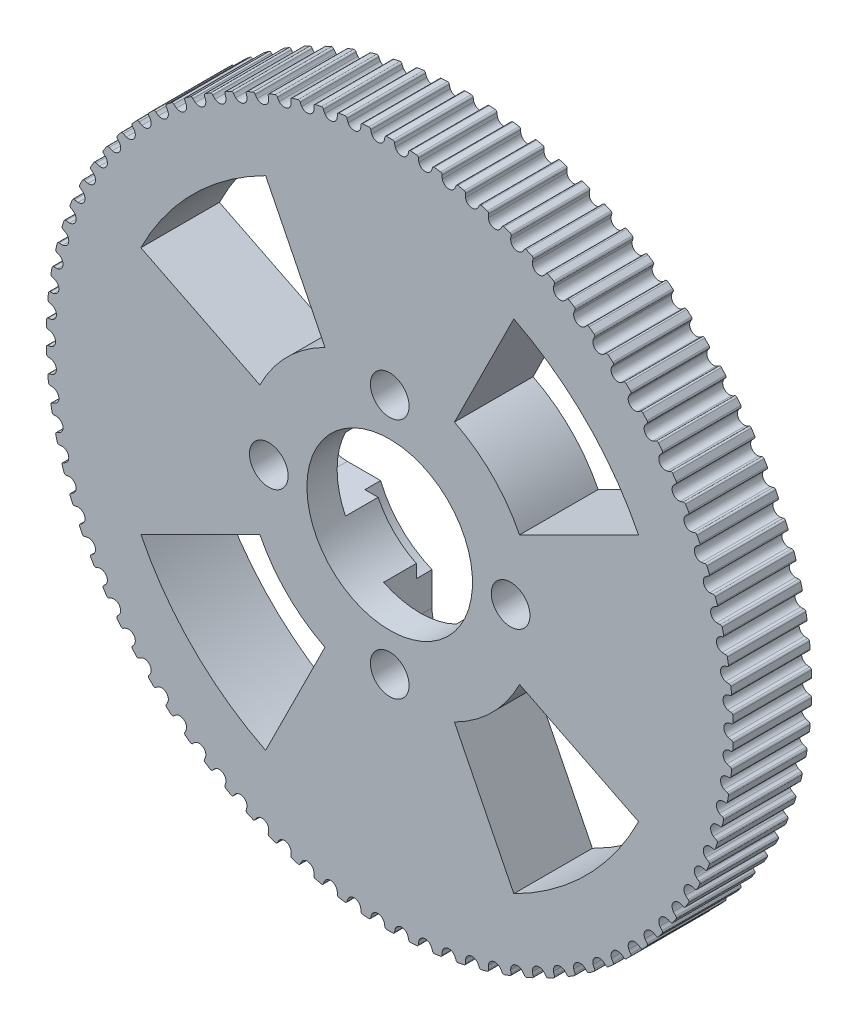
SolidWorks part; units mm, degrees
ref_plane "前视基准面" through (0, 0, 0) normal (0, 0, 1) x (1, 0, 0)
ref_plane "上视基准面" through (0, 0, 0) normal (0, 1, 0) x (1, 0, 0)
ref_plane "右视基准面" through (0, 0, 0) normal (1, 0, 0) x (0, 0, -1)
sketch "草图1" plane through (0, 0, 0) normal (0, 0, 1) x (1, 0, 0)
  line L0 (-10.0057, 26.1448) -> (-10.0057, 26.1386)
  line L1 (-10.0057, -26.1386) -> (-10.0057, -26.1448)
  arc A0 (27.4975, -7.1209) -> (27.6219, -6.6219) centre (0.0103, -0.0026) ccw
  arc A1 (27.6219, -6.6219) -> (27.626, -6.587) centre (27.476, -6.587) ccw
  arc A2 (27.626, -6.587) -> (27.5209, -6.4438) centre (27.476, -6.587) ccw
  arc A3 (27.2702, -6.3249) -> (27.5209, -6.4438) centre (27.82, -5.4896) ccw
  arc A4 (27.4851, -5.3137) -> (27.2702, -6.3249) centre (27.5753, -5.8613) ccw
  arc A5 (27.7625, -5.307) -> (27.4851, -5.3137) centre (27.6477, -6.3004) ccw
  arc A6 (27.7625, -5.307) -> (27.9272, -5.1854) centre (27.7797, -5.158) ccw
  arc A7 (27.9272, -5.1854) -> (28.0165, -4.679) centre (0.0105, -0.0018) ccw
  arc A8 (28.0165, -4.679) -> (28.0186, -4.6543) centre (27.8686, -4.6543) ccw
  arc A9 (28.0186, -4.6543) -> (27.9033, -4.5084) centre (27.8686, -4.6543) ccw
  arc A10 (27.6449, -4.4072) -> (27.9033, -4.5084) centre (28.1352, -3.5356) ccw
  arc A11 (27.7888, -3.3835) -> (27.6449, -4.4072) centre (27.917, -3.9235) ccw
  arc A12 (28.0651, -3.3575) -> (27.7888, -3.3835) centre (28.0198, -4.3564) ccw
  arc A13 (28.0651, -3.3575) -> (28.2209, -3.2247) centre (28.0719, -3.2076) ccw
  arc A14 (28.2209, -3.2247) -> (28.2747, -2.7133) centre (0.0106, -0.0011) ccw
  arc A15 (28.2747, -2.7133) -> (28.2753, -2.6989) centre (28.1253, -2.6989) ccw
  arc A16 (28.2753, -2.6989) -> (28.1499, -2.551) centre (28.1253, -2.6989) ccw
  arc A17 (27.885, -2.4681) -> (28.1499, -2.551) centre (28.3133, -1.5644) ccw
  arc A18 (27.9571, -1.4368) -> (27.885, -2.4681) centre (28.1227, -1.9665) ccw
  arc A19 (28.2309, -1.3916) -> (27.9571, -1.4368) centre (28.2554, -2.3913) ccw
  arc A20 (28.2309, -1.3916) -> (28.3771, -1.2482) centre (28.2272, -1.2416) ccw
  arc A21 (28.3771, -1.2482) -> (28.395, -0.7343) centre (0.0106, -0.0004) ccw
  arc A22 (28.395, -0.7343) -> (28.3951, -0.7304) centre (28.2451, -0.7304) ccw
  arc A23 (28.3951, -0.7304) -> (28.2592, -0.5811) centre (28.2451, -0.7304) ccw
  arc A24 (27.9893, -0.5169) -> (28.2592, -0.5811) centre (28.3534, 0.4144) ccw
  arc A25 (27.9893, 0.5169) -> (27.9893, -0.5169) centre (28.1914, 0) ccw
  arc A26 (28.2592, 0.5811) -> (27.9893, 0.5169) centre (28.3534, -0.4144) ccw
  arc A27 (28.2592, 0.5811) -> (28.3951, 0.7304) centre (28.2451, 0.7304) ccw
  arc A28 (28.3951, 0.7304) -> (28.395, 0.7343) centre (28.2451, 0.7304) ccw
  arc A29 (28.395, 0.7343) -> (28.3771, 1.2482) centre (0.0106, 0.0004) ccw
  arc A30 (28.3771, 1.2482) -> (28.2309, 1.3916) centre (28.2272, 1.2416) ccw
  arc A31 (27.9571, 1.4368) -> (28.2309, 1.3916) centre (28.2554, 2.3913) ccw
  arc A32 (27.885, 2.4681) -> (27.9571, 1.4368) centre (28.1227, 1.9665) ccw
  arc A33 (28.1499, 2.551) -> (27.885, 2.4681) centre (28.3133, 1.5644) ccw
  arc A34 (28.1499, 2.551) -> (28.2753, 2.6989) centre (28.1253, 2.6989) ccw
  arc A35 (28.2753, 2.6989) -> (28.2747, 2.7133) centre (28.1253, 2.6989) ccw
  arc A36 (28.2747, 2.7133) -> (28.2209, 3.2247) centre (0.0106, 0.0011) ccw
  arc A37 (28.2209, 3.2247) -> (28.0651, 3.3575) centre (28.0719, 3.2076) ccw
  arc A38 (27.7888, 3.3835) -> (28.0651, 3.3575) centre (28.0198, 4.3564) ccw
  arc A39 (27.6449, 4.4072) -> (27.7888, 3.3835) centre (27.917, 3.9235) ccw
  arc A40 (27.9033, 4.5084) -> (27.6449, 4.4072) centre (28.1352, 3.5356) ccw
  arc A41 (27.9033, 4.5084) -> (28.0186, 4.6543) centre (27.8686, 4.6543) ccw
  arc A42 (28.0186, 4.6543) -> (28.0165, 4.679) centre (27.8686, 4.6543) ccw
  arc A43 (28.0165, 4.679) -> (27.9272, 5.1854) centre (0.0105, 0.0018) ccw
  arc A44 (27.9272, 5.1854) -> (27.7625, 5.307) centre (27.7797, 5.158) ccw
  arc A45 (27.4851, 5.3137) -> (27.7625, 5.307) centre (27.6477, 6.3004) ccw
  arc A46 (27.2702, 6.3249) -> (27.4851, 5.3137) centre (27.5753, 5.8613) ccw
  arc A47 (27.5209, 6.4438) -> (27.2702, 6.3249) centre (27.82, 5.4896) ccw
  arc A48 (27.5209, 6.4438) -> (27.626, 6.587) centre (27.476, 6.587) ccw
  arc A49 (27.626, 6.587) -> (27.6219, 6.6219) centre (27.476, 6.587) ccw
  arc A50 (27.6219, 6.6219) -> (27.4975, 7.1209) centre (0.0103, 0.0026) ccw
  arc A51 (27.4975, 7.1209) -> (27.3247, 7.2307) centre (27.3523, 7.0833) ccw
  arc A52 (27.0475, 7.218) -> (27.3247, 7.2307) centre (27.1408, 8.2137) ccw
  arc A53 (26.7625, 8.2117) -> (27.0475, 7.218) centre (27.0993, 7.7706) ccw
  arc A54 (27.0043, 8.3479) -> (26.7625, 8.2117) centre (27.3693, 7.4169) ccw
  arc A55 (27.0043, 8.3479) -> (27.0996, 8.4876) centre (26.9496, 8.4876) ccw
  arc A56 (27.0996, 8.4876) -> (27.0927, 8.5326) centre (26.9496, 8.4876) ccw
  arc A57 (27.0927, 8.5326) -> (26.9338, 9.0216) centre (0.0101, 0.0033) ccw
  arc A58 (26.9338, 9.0216) -> (26.7537, 9.1192) centre (26.7915, 8.974) ccw
  arc A59 (26.4781, 9.0872) -> (26.7537, 9.1192) centre (26.5018, 10.0869) ccw
  arc A60 (26.1245, 10.0586) -> (26.4781, 9.0872) centre (26.4912, 9.642) ccw
  arc A61 (26.3562, 10.2113) -> (26.1245, 10.0586) centre (26.7853, 9.308) ccw
  arc A62 (26.3562, 10.2113) -> (26.4419, 10.3468) centre (26.2919, 10.3468) ccw
  arc A63 (26.4419, 10.3468) -> (26.4315, 10.4017) centre (26.2919, 10.3468) ccw
  arc A64 (26.4315, 10.4017) -> (26.2388, 10.8785) centre (0.0099, 0.004) ccw
  arc A65 (26.2388, 10.8785) -> (26.0524, 10.9632) centre (26.1003, 10.821) ccw
  arc A66 (25.7797, 10.9121) -> (26.0524, 10.9632) centre (25.7336, 11.911) ccw
  arc A67 (25.3592, 11.8565) -> (25.7797, 10.9121) centre (25.7541, 11.4665) ccw
  arc A68 (25.5797, 12.0249) -> (25.3592, 11.8565) centre (26.0707, 11.1538) ccw
  arc A69 (25.5797, 12.0249) -> (25.6561, 12.1556) centre (25.5061, 12.1556) ccw
  arc A70 (25.6561, 12.1556) -> (25.6415, 12.2201) centre (25.5061, 12.1556) ccw
  arc A71 (25.6415, 12.2201) -> (25.4161, 12.6823) centre (0.0096, 0.0047) ccw
  arc A72 (25.4161, 12.6823) -> (25.2242, 12.7538) centre (25.2819, 12.6153) ccw
  arc A73 (24.9557, 12.6838) -> (25.2242, 12.7538) centre (24.84, 13.6771) ccw
  arc A74 (24.4704, 13.5965) -> (24.9557, 12.6838) centre (24.8915, 13.235) ccw
  arc A75 (24.6786, 13.78) -> (24.4704, 13.5965) centre (25.2292, 12.9452) ccw
  arc A76 (24.6786, 13.78) -> (24.746, 13.9052) centre (24.596, 13.9052) ccw
  arc A77 (24.746, 13.9052) -> (24.7266, 13.979) centre (24.596, 13.9052) ccw
  arc A78 (24.7266, 13.979) -> (24.4695, 14.4243) centre (0.0092, 0.0053) ccw
  arc A79 (24.4695, 14.4243) -> (24.2731, 14.4823) centre (24.3403, 14.3482) ccw
  arc A80 (24.0101, 14.3937) -> (24.2731, 14.4823) centre (23.8254, 15.3765) ccw
  arc A81 (23.4623, 15.2704) -> (24.0101, 14.3937) centre (23.9076, 14.9391) ccw
  arc A82 (23.6572, 15.4679) -> (23.4623, 15.2704) centre (24.2647, 14.6736) ccw
  arc A83 (23.6572, 15.4679) -> (23.7161, 15.5871) centre (23.5661, 15.5871) ccw
  arc A84 (23.7161, 15.5871) -> (23.6912, 15.6698) centre (23.5661, 15.5871) ccw
  arc A85 (23.6912, 15.6698) -> (23.4037, 16.0961) centre (0.0088, 0.006) ccw
  arc A86 (23.4037, 16.0961) -> (23.2038, 16.1402) centre (23.2801, 16.0111) ccw
  arc A87 (22.9476, 16.0335) -> (23.2038, 16.1402) centre (22.6948, 17.001) ccw
  arc A88 (22.34, 16.8698) -> (22.9476, 16.0335) centre (22.8073, 16.5705) ccw
  arc A89 (22.5206, 17.0805) -> (22.34, 16.8698) centre (23.182, 16.3304) ccw
  arc A90 (22.5206, 17.0805) -> (22.5714, 17.193) centre (22.4214, 17.193) ccw
  arc A91 (22.5714, 17.193) -> (22.5405, 17.2843) centre (22.4214, 17.193) ccw
  arc A92 (22.5405, 17.2843) -> (22.2239, 17.6895) centre (0.0084, 0.0066) ccw
  arc A93 (22.2239, 17.6895) -> (22.0214, 17.7195) centre (22.1065, 17.596) ccw
  arc A94 (21.7733, 17.5952) -> (22.0214, 17.7195) centre (21.4536, 18.5427) ccw
  arc A95 (21.1088, 18.3871) -> (21.7733, 17.5952) centre (21.5958, 18.1211) ccw
  arc A96 (21.2743, 18.6098) -> (21.1088, 18.3871) centre (21.9864, 17.9077) ccw
  arc A97 (21.2743, 18.6098) -> (21.3175, 18.7152) centre (21.1675, 18.7152) ccw
  arc A98 (21.3175, 18.7152) -> (21.2799, 18.8145) centre (21.1675, 18.7152) ccw
  arc A99 (21.2799, 18.8145) -> (20.9358, 19.1966) centre (0.0079, 0.0071) ccw
  arc A100 (20.9358, 19.1966) -> (20.7317, 19.2125) centre (20.8252, 19.0953) ccw
  arc A101 (20.4928, 19.0711) -> (20.7317, 19.2125) centre (20.1079, 19.9941) ccw
  arc A102 (19.7747, 19.8148) -> (20.4928, 19.0711) centre (20.2792, 19.5834) ccw
  arc A103 (19.9243, 20.0485) -> (19.7747, 19.8148) centre (20.6836, 19.3978) ccw
  arc A104 (19.9243, 20.0485) -> (19.9604, 20.1461) centre (19.8104, 20.1461) ccw
  arc A105 (19.9604, 20.1461) -> (19.9156, 20.2531) centre (19.8104, 20.1461) ccw
  arc A106 (19.9156, 20.2531) -> (19.5457, 20.6103) centre (0.0074, 0.0077) ccw
  arc A107 (19.5457, 20.6103) -> (19.341, 20.6119) centre (19.4425, 20.5014) ccw
  arc A108 (19.1126, 20.4542) -> (19.341, 20.6119) centre (18.6642, 21.348) ccw
  arc A109 (18.3443, 21.1459) -> (19.1126, 20.4542) centre (18.8637, 20.9503) ccw
  arc A110 (18.4773, 21.3895) -> (18.3443, 21.1459) centre (19.2801, 20.7934) ccw
  arc A111 (18.4773, 21.3895) -> (18.5068, 21.479) centre (18.3568, 21.479) ccw
  arc A112 (18.5068, 21.479) -> (18.4543, 21.593) centre (18.3568, 21.479) ccw
  arc A113 (18.4543, 21.593) -> (18.0604, 21.9235) centre (0.0068, 0.0082) ccw
  arc A114 (18.0604, 21.9235) -> (17.856, 21.9108) centre (17.965, 21.8077) ccw
  arc A115 (17.6392, 21.7376) -> (17.856, 21.9108) centre (17.1295, 22.598) ccw
  arc A116 (16.8246, 22.3741) -> (17.6392, 21.7376) centre (17.3563, 22.2151) ccw
  arc A117 (16.9402, 22.6263) -> (16.8246, 22.3741) centre (17.7827, 22.0876) ccw
  arc A118 (16.9402, 22.6263) -> (16.9638, 22.7071) centre (16.8138, 22.7071) ccw
  arc A119 (16.9638, 22.7071) -> (16.9031, 22.8277) centre (16.8138, 22.7071) ccw
  arc A120 (16.9031, 22.8277) -> (16.4871, 23.1299) centre (0.0063, 0.0086) ccw
  arc A121 (16.4871, 23.1299) -> (16.2841, 23.103) centre (16.4, 23.0078) ccw
  arc A122 (16.0799, 22.9151) -> (16.2841, 23.103) centre (15.5114, 23.7378) ccw
  arc A123 (15.2229, 23.4932) -> (16.0799, 22.9151) centre (15.7644, 23.3717) ccw
  arc A124 (15.3206, 23.7529) -> (15.2229, 23.4932) centre (16.1986, 23.2743) ccw
  arc A125 (15.3206, 23.7529) -> (15.3389, 23.8247) centre (15.1889, 23.8247) ccw
  arc A126 (15.3389, 23.8247) -> (15.2695, 23.9512) centre (15.1889, 23.8247) ccw
  arc A127 (15.2695, 23.9512) -> (14.8335, 24.2237) centre (0.0056, 0.009) ccw
  arc A128 (14.8335, 24.2237) -> (14.6329, 24.1827) centre (14.7551, 24.0957) ccw
  arc A129 (14.4423, 23.981) -> (14.6329, 24.1827) centre (13.8178, 24.762) ccw
  arc A130 (13.547, 24.4978) -> (14.4423, 23.981) centre (14.0957, 24.4144) ccw
  arc A131 (13.6264, 24.7638) -> (13.547, 24.4978) centre (14.5356, 24.3476) ccw
  arc A132 (13.6264, 24.7638) -> (13.64, 24.8262) centre (13.49, 24.8262) ccw
  arc A133 (13.64, 24.8262) -> (13.5616, 24.958) centre (13.49, 24.8262) ccw
  arc A134 (13.5616, 24.958) -> (13.1076, 25.1994) centre (0.005, 0.0094) ccw
  arc A135 (13.1076, 25.1994) -> (12.9103, 25.1445) centre (13.0384, 25.0663) ccw
  arc A136 (12.7343, 24.93) -> (12.9103, 25.1445) centre (12.0568, 25.6656) ccw
  arc A137 (11.8051, 25.3832) -> (12.7343, 24.93) centre (12.3583, 25.3382) ccw
  arc A138 (11.8657, 25.654) -> (11.8051, 25.3832) centre (12.8018, 25.3022) ccw
  arc A139 (11.8657, 25.654) -> (11.8753, 25.7067) centre (11.7253, 25.7067) ccw
  arc A140 (11.8753, 25.7067) -> (11.7876, 25.8432) centre (11.7253, 25.7067) ccw
  arc A141 (11.7876, 25.8432) -> (11.3178, 26.0523) centre (0.0043, 0.0097) ccw
  arc A142 (11.3178, 26.0523) -> (11.1249, 25.9838) centre (11.2581, 25.9148) ccw
  arc A143 (10.9642, 25.7576) -> (11.1249, 25.9838) centre (10.2371, 26.4441) ccw
  arc A144 (10.0057, 26.1448) -> (10.9642, 25.7576) centre (10.5607, 26.1386) ccw
  arc A145 (10.0473, 26.4192) -> (10.0057, 26.1448) centre (11.0056, 26.1336) ccw
  arc A146 (10.0473, 26.4192) -> (10.0535, 26.462) centre (9.9035, 26.462) ccw
  arc A147 (10.0535, 26.462) -> (9.9561, 26.6025) centre (9.9035, 26.462) ccw
  arc A148 (9.9561, 26.6025) -> (9.4729, 26.7784) centre (0.0036, 0.01) ccw
  arc A149 (9.4729, 26.7784) -> (9.2853, 26.6965) centre (9.4229, 26.637) ccw
  arc A150 (9.1407, 26.4596) -> (9.2853, 26.6965) centre (8.3675, 27.0938) ccw
  arc A151 (8.1576, 26.7791) -> (9.1407, 26.4596) centre (8.7116, 26.8116) ccw
  arc A152 (8.1558, 26.8376) -> (8.1576, 26.7791) centre (9.1558, 26.8376) ccw
  arc A153 (8.1799, 27.0557) -> (8.1558, 26.8376) centre (9.1558, 26.8376) ccw
  arc A154 (8.1799, 27.0557) -> (8.1835, 27.0884) centre (8.0335, 27.0884) ccw
  arc A155 (8.1835, 27.0884) -> (8.0762, 27.2322) centre (8.0335, 27.0884) ccw
  arc A156 (8.0762, 27.2322) -> (7.5819, 27.3739) centre (0.0029, 0.0102) ccw
  arc A157 (7.5819, 27.3739) -> (7.4004, 27.2792) centre (7.5419, 27.2294) ccw
  arc A158 (7.2727, 27.0328) -> (7.4004, 27.2792) centre (6.4572, 27.6115) ccw
  arc A159 (6.2697, 27.2829) -> (7.2727, 27.0328) centre (6.8201, 27.354) ccw
  arc A160 (6.2614, 27.4109) -> (6.2697, 27.2829) centre (7.2614, 27.4109) ccw
  arc A161 (6.2727, 27.5604) -> (6.2614, 27.4109) centre (7.2614, 27.4109) ccw
  arc A162 (6.2727, 27.5604) -> (6.2744, 27.5828) centre (6.1244, 27.5828) ccw
  arc A163 (6.2744, 27.5828) -> (6.1569, 27.7292) centre (6.1244, 27.5828) ccw
  arc A164 (6.1569, 27.7292) -> (5.6539, 27.8361) centre (0.0022, 0.0104) ccw
  arc A165 (5.6539, 27.8361) -> (5.4794, 27.729) centre (5.6241, 27.6892) ccw
  arc A166 (5.3693, 27.4743) -> (5.4794, 27.729) centre (4.5154, 27.9946) ccw
  arc A167 (4.3512, 27.6538) -> (5.3693, 27.4743) centre (4.8954, 27.7631) ccw
  arc A168 (4.3317, 27.8507) -> (4.3512, 27.6538) centre (5.3317, 27.8507) ccw
  arc A169 (4.3349, 27.9308) -> (4.3317, 27.8507) centre (5.3317, 27.8507) ccw
  arc A170 (4.3349, 27.9308) -> (4.3354, 27.9428) centre (4.1854, 27.9428) ccw
  arc A171 (4.3354, 27.9428) -> (4.2076, 28.0912) centre (4.1854, 27.9428) ccw
  arc A172 (4.2076, 28.0912) -> (3.6984, 28.1627) centre (0.0015, 0.0105) ccw
  arc A173 (3.6984, 28.1627) -> (3.5318, 28.0437) centre (3.6789, 28.014) ccw
  arc A174 (3.4397, 27.7819) -> (3.5318, 28.0437) centre (2.5516, 28.2414) ccw
  arc A175 (2.4116, 27.89) -> (3.4397, 27.7819) centre (2.9468, 28.0369) ccw
  arc A176 (2.3759, 28.1548) -> (2.4116, 27.89) centre (3.3759, 28.1548) ccw
  arc A177 (2.376, 28.1652) -> (2.3759, 28.1548) centre (3.3759, 28.1548) ccw
  arc A178 (2.376, 28.1652) -> (2.2378, 28.3163) centre (2.226, 28.1667) ccw
  arc A179 (2.2378, 28.3163) -> (1.7248, 28.3521) centre (0.0007, 0.0106) ccw
  arc A180 (1.7248, 28.3521) -> (1.567, 28.2217) centre (1.7157, 28.2024) ccw
  arc A181 (1.4934, 27.9542) -> (1.567, 28.2217) centre (0.5753, 28.3506) ccw
  arc A182 (0.4602, 27.9902) -> (1.4934, 27.9542) centre (0.9839, 28.1742) ccw
  arc A183 (0.4055, 28.2623) -> (0.4602, 27.9902) centre (1.4037, 28.3217) ccw
  arc A184 (0.4055, 28.2623) -> (0.2571, 28.4034) centre (0.2557, 28.2534) ccw
  arc A185 (0.2571, 28.4034) -> (-0.2571, 28.4034) centre (0, 0.0107) ccw
  arc A186 (-0.2571, 28.4034) -> (-0.4055, 28.2623) centre (-0.2557, 28.2534) ccw
  arc A187 (-0.4602, 27.9902) -> (-0.4055, 28.2623) centre (-1.4037, 28.3217) ccw
  arc A188 (-1.4934, 27.9542) -> (-0.4602, 27.9902) centre (-0.9839, 28.1742) ccw
  arc A189 (-1.567, 28.2217) -> (-1.4934, 27.9542) centre (-0.5753, 28.3506) ccw
  arc A190 (-1.567, 28.2217) -> (-1.7248, 28.3521) centre (-1.7157, 28.2024) ccw
  arc A191 (-1.7248, 28.3521) -> (-2.2378, 28.3163) centre (-0.0007, 0.0106) ccw
  arc A192 (-2.2378, 28.3163) -> (-2.376, 28.1652) centre (-2.226, 28.1667) ccw
  arc A193 (-2.4116, 27.89) -> (-2.376, 28.1652) centre (-3.3759, 28.1548) ccw
  arc A194 (-3.4397, 27.7819) -> (-2.4116, 27.89) centre (-2.9468, 28.0369) ccw
  arc A195 (-3.5318, 28.0437) -> (-3.4397, 27.7819) centre (-2.5516, 28.2414) ccw
  arc A196 (-3.5318, 28.0437) -> (-3.6984, 28.1627) centre (-3.6789, 28.014) ccw
  arc A197 (-3.6984, 28.1627) -> (-4.2076, 28.0912) centre (-0.0015, 0.0105) ccw
  arc A198 (-4.2076, 28.0912) -> (-4.3349, 27.9308) centre (-4.1854, 27.9428) ccw
  arc A199 (-4.3512, 27.6538) -> (-4.3349, 27.9308) centre (-5.3317, 27.8507) ccw
  arc A200 (-5.3693, 27.4743) -> (-4.3512, 27.6538) centre (-4.8954, 27.7631) ccw
  arc A201 (-5.4794, 27.729) -> (-5.3693, 27.4743) centre (-4.5154, 27.9946) ccw
  arc A202 (-5.4794, 27.729) -> (-5.6539, 27.8361) centre (-5.6241, 27.6892) ccw
  arc A203 (-5.6539, 27.8361) -> (-6.1569, 27.7292) centre (-0.0022, 0.0104) ccw
  arc A204 (-6.1569, 27.7292) -> (-6.2727, 27.5604) centre (-6.1244, 27.5828) ccw
  arc A205 (-6.2697, 27.2829) -> (-6.2727, 27.5604) centre (-7.2614, 27.4109) ccw
  arc A206 (-7.2727, 27.0328) -> (-6.2697, 27.2829) centre (-6.8201, 27.354) ccw
  arc A207 (-7.4004, 27.2792) -> (-7.2727, 27.0328) centre (-6.4572, 27.6115) ccw
  arc A208 (-7.4004, 27.2792) -> (-7.5819, 27.3739) centre (-7.5419, 27.2294) ccw
  arc A209 (-7.5819, 27.3739) -> (-8.0762, 27.2322) centre (-0.0029, 0.0102) ccw
  arc A210 (-8.0762, 27.2322) -> (-8.1799, 27.0557) centre (-8.0335, 27.0884) ccw
  arc A211 (-8.1576, 26.7791) -> (-8.1799, 27.0557) centre (-9.1558, 26.8376) ccw
  arc A212 (-9.1407, 26.4596) -> (-8.1576, 26.7791) centre (-8.7116, 26.8116) ccw
  arc A213 (-9.2853, 26.6965) -> (-9.1407, 26.4596) centre (-8.3675, 27.0938) ccw
  arc A214 (-9.2853, 26.6965) -> (-9.4729, 26.7784) centre (-9.4229, 26.637) ccw
  arc A215 (-9.4729, 26.7784) -> (-9.9561, 26.6025) centre (-0.0036, 0.01) ccw
  arc A216 (-9.9561, 26.6025) -> (-10.0473, 26.4192) centre (-9.9035, 26.462) ccw
  arc A217 (-10.0057, 26.1448) -> (-10.0473, 26.4192) centre (-11.0056, 26.1336) ccw
  arc A218 (-10.9642, 25.7576) -> (-10.0057, 26.1386) centre (-10.5607, 26.1386) ccw
  arc A219 (-11.1249, 25.9838) -> (-10.9642, 25.7576) centre (-10.2371, 26.4441) ccw
  arc A220 (-11.1249, 25.9838) -> (-11.3178, 26.0523) centre (-11.2581, 25.9148) ccw
  arc A221 (-11.3178, 26.0523) -> (-11.7876, 25.8432) centre (-0.0043, 0.0097) ccw
  arc A222 (-11.7876, 25.8432) -> (-11.8657, 25.654) centre (-11.7253, 25.7067) ccw
  arc A223 (-11.8051, 25.3832) -> (-11.8657, 25.654) centre (-12.8018, 25.3022) ccw
  arc A224 (-11.8033, 25.3382) -> (-11.8051, 25.3832) centre (-12.3583, 25.3382) ccw
  arc A225 (-12.7343, 24.93) -> (-11.8033, 25.3382) centre (-12.3583, 25.3382) ccw
  arc A226 (-12.9103, 25.1445) -> (-12.7343, 24.93) centre (-12.0568, 25.6656) ccw
  arc A227 (-12.9103, 25.1445) -> (-13.1076, 25.1994) centre (-13.0384, 25.0663) ccw
  arc A228 (-13.1076, 25.1994) -> (-13.5616, 24.958) centre (-0.005, 0.0094) ccw
  arc A229 (-13.5616, 24.958) -> (-13.6264, 24.7638) centre (-13.49, 24.8262) ccw
  arc A230 (-13.547, 24.4978) -> (-13.6264, 24.7638) centre (-14.5356, 24.3476) ccw
  arc A231 (-13.5407, 24.4144) -> (-13.547, 24.4978) centre (-14.0957, 24.4144) ccw
  arc A232 (-14.4423, 23.981) -> (-13.5407, 24.4144) centre (-14.0957, 24.4144) ccw
  arc A233 (-14.6329, 24.1827) -> (-14.4423, 23.981) centre (-13.8178, 24.762) ccw
  arc A234 (-14.6329, 24.1827) -> (-14.8335, 24.2237) centre (-14.7551, 24.0957) ccw
  arc A235 (-14.8335, 24.2237) -> (-15.2695, 23.9512) centre (-0.0056, 0.009) ccw
  arc A236 (-15.2695, 23.9512) -> (-15.3206, 23.7529) centre (-15.1889, 23.8247) ccw
  arc A237 (-15.2229, 23.4932) -> (-15.3206, 23.7529) centre (-16.1986, 23.2743) ccw
  arc A238 (-15.2094, 23.3717) -> (-15.2229, 23.4932) centre (-15.7644, 23.3717) ccw
  arc A239 (-16.0799, 22.9151) -> (-15.2094, 23.3717) centre (-15.7644, 23.3717) ccw
  arc A240 (-16.2841, 23.103) -> (-16.0799, 22.9151) centre (-15.5114, 23.7378) ccw
  arc A241 (-16.2841, 23.103) -> (-16.4871, 23.1299) centre (-16.4, 23.0078) ccw
  arc A242 (-16.4871, 23.1299) -> (-16.9031, 22.8277) centre (-0.0063, 0.0086) ccw
  arc A243 (-16.9031, 22.8277) -> (-16.9402, 22.6263) centre (-16.8138, 22.7071) ccw
  arc A244 (-16.8246, 22.3741) -> (-16.9402, 22.6263) centre (-17.7827, 22.0876) ccw
  arc A245 (-16.8013, 22.2151) -> (-16.8246, 22.3741) centre (-17.3563, 22.2151) ccw
  arc A246 (-17.6392, 21.7376) -> (-16.8013, 22.2151) centre (-17.3563, 22.2151) ccw
  arc A247 (-17.856, 21.9108) -> (-17.6392, 21.7376) centre (-17.1295, 22.598) ccw
  arc A248 (-17.856, 21.9108) -> (-18.0604, 21.9235) centre (-17.965, 21.8077) ccw
  arc A249 (-18.0604, 21.9235) -> (-18.4543, 21.593) centre (-0.0068, 0.0082) ccw
  arc A250 (-18.4543, 21.593) -> (-18.4773, 21.3895) centre (-18.3568, 21.479) ccw
  arc A251 (-18.3443, 21.1459) -> (-18.4773, 21.3895) centre (-19.2801, 20.7934) ccw
  arc A252 (-18.3087, 20.9503) -> (-18.3443, 21.1459) centre (-18.8637, 20.9503) ccw
  arc A253 (-19.1126, 20.4542) -> (-18.3087, 20.9503) centre (-18.8637, 20.9503) ccw
  arc A254 (-19.341, 20.6119) -> (-19.1126, 20.4542) centre (-18.6642, 21.348) ccw
  arc A255 (-19.341, 20.6119) -> (-19.5457, 20.6103) centre (-19.4425, 20.5014) ccw
  arc A256 (-19.5457, 20.6103) -> (-19.9156, 20.2531) centre (-0.0074, 0.0077) ccw
  arc A257 (-19.9156, 20.2531) -> (-19.9243, 20.0485) centre (-19.8104, 20.1461) ccw
  arc A258 (-19.7747, 19.8148) -> (-19.9243, 20.0485) centre (-20.6836, 19.3978) ccw
  arc A259 (-19.7242, 19.5834) -> (-19.7747, 19.8148) centre (-20.2792, 19.5834) ccw
  arc A260 (-20.4928, 19.0711) -> (-19.7242, 19.5834) centre (-20.2792, 19.5834) ccw
  arc A261 (-20.7317, 19.2125) -> (-20.4928, 19.0711) centre (-20.1079, 19.9941) ccw
  arc A262 (-20.7317, 19.2125) -> (-20.9358, 19.1966) centre (-20.8252, 19.0953) ccw
  arc A263 (-20.9358, 19.1966) -> (-21.2799, 18.8145) centre (-0.0079, 0.0071) ccw
  arc A264 (-21.2799, 18.8145) -> (-21.2743, 18.6098) centre (-21.1675, 18.7152) ccw
  arc A265 (-21.1088, 18.3871) -> (-21.2743, 18.6098) centre (-21.9864, 17.9077) ccw
  arc A266 (-21.0408, 18.1211) -> (-21.1088, 18.3871) centre (-21.5958, 18.1211) ccw
  arc A267 (-21.7733, 17.5952) -> (-21.0408, 18.1211) centre (-21.5958, 18.1211) ccw
  arc A268 (-22.0214, 17.7195) -> (-21.7733, 17.5952) centre (-21.4536, 18.5427) ccw
  arc A269 (-22.0214, 17.7195) -> (-22.2239, 17.6895) centre (-22.1065, 17.596) ccw
  arc A270 (-22.2239, 17.6895) -> (-22.5405, 17.2843) centre (-0.0084, 0.0066) ccw
  arc A271 (-22.5405, 17.2843) -> (-22.5206, 17.0805) centre (-22.4214, 17.193) ccw
  arc A272 (-22.34, 16.8698) -> (-22.5206, 17.0805) centre (-23.182, 16.3304) ccw
  arc A273 (-22.2523, 16.5705) -> (-22.34, 16.8698) centre (-22.8073, 16.5705) ccw
  arc A274 (-22.9476, 16.0335) -> (-22.2523, 16.5705) centre (-22.8073, 16.5705) ccw
  arc A275 (-23.2038, 16.1402) -> (-22.9476, 16.0335) centre (-22.6948, 17.001) ccw
  arc A276 (-23.2038, 16.1402) -> (-23.4037, 16.0961) centre (-23.2801, 16.0111) ccw
  arc A277 (-23.4037, 16.0961) -> (-23.6912, 15.6698) centre (-0.0088, 0.006) ccw
  arc A278 (-23.6912, 15.6698) -> (-23.6572, 15.4679) centre (-23.5661, 15.5871) ccw
  arc A279 (-23.4623, 15.2704) -> (-23.6572, 15.4679) centre (-24.2647, 14.6736) ccw
  arc A280 (-23.3526, 14.9391) -> (-23.4623, 15.2704) centre (-23.9076, 14.9391) ccw
  arc A281 (-24.0101, 14.3937) -> (-23.3526, 14.9391) centre (-23.9076, 14.9391) ccw
  arc A282 (-24.2731, 14.4823) -> (-24.0101, 14.3937) centre (-23.8254, 15.3765) ccw
  arc A283 (-24.2731, 14.4823) -> (-24.4695, 14.4243) centre (-24.3403, 14.3482) ccw
  arc A284 (-24.4695, 14.4243) -> (-24.7266, 13.979) centre (-0.0092, 0.0053) ccw
  arc A285 (-24.7266, 13.979) -> (-24.6786, 13.78) centre (-24.596, 13.9052) ccw
  arc A286 (-24.4704, 13.5965) -> (-24.6786, 13.78) centre (-25.2292, 12.9452) ccw
  arc A287 (-24.3365, 13.235) -> (-24.4704, 13.5965) centre (-24.8915, 13.235) ccw
  arc A288 (-24.9557, 12.6838) -> (-24.3365, 13.235) centre (-24.8915, 13.235) ccw
  arc A289 (-25.2242, 12.7538) -> (-24.9557, 12.6838) centre (-24.84, 13.6771) ccw
  arc A290 (-25.2242, 12.7538) -> (-25.4161, 12.6823) centre (-25.2819, 12.6153) ccw
  arc A291 (-25.4161, 12.6823) -> (-25.6415, 12.2201) centre (-0.0096, 0.0047) ccw
  arc A292 (-25.6415, 12.2201) -> (-25.5797, 12.0249) centre (-25.5061, 12.1556) ccw
  arc A293 (-25.3592, 11.8565) -> (-25.5797, 12.0249) centre (-26.0707, 11.1538) ccw
  arc A294 (-25.1991, 11.4665) -> (-25.3592, 11.8565) centre (-25.7541, 11.4665) ccw
  arc A295 (-25.7797, 10.9121) -> (-25.1991, 11.4665) centre (-25.7541, 11.4665) ccw
  arc A296 (-26.0524, 10.9632) -> (-25.7797, 10.9121) centre (-25.7336, 11.911) ccw
  arc A297 (-26.0524, 10.9632) -> (-26.2388, 10.8785) centre (-26.1003, 10.821) ccw
  arc A298 (-26.2388, 10.8785) -> (-26.4315, 10.4017) centre (-0.0099, 0.004) ccw
  arc A299 (-26.4315, 10.4017) -> (-26.3562, 10.2113) centre (-26.2919, 10.3468) ccw
  arc A300 (-26.1245, 10.0586) -> (-26.3562, 10.2113) centre (-26.7853, 9.308) ccw
  arc A301 (-25.9362, 9.642) -> (-26.1245, 10.0586) centre (-26.4912, 9.642) ccw
  arc A302 (-26.4781, 9.0872) -> (-25.9362, 9.642) centre (-26.4912, 9.642) ccw
  arc A303 (-26.7537, 9.1192) -> (-26.4781, 9.0872) centre (-26.5018, 10.0869) ccw
  arc A304 (-26.7537, 9.1192) -> (-26.9338, 9.0216) centre (-26.7915, 8.974) ccw
  arc A305 (-26.9338, 9.0216) -> (-27.0927, 8.5326) centre (-0.0101, 0.0033) ccw
  arc A306 (-27.0927, 8.5326) -> (-27.0043, 8.3479) centre (-26.9496, 8.4876) ccw
  arc A307 (-26.7625, 8.2117) -> (-27.0043, 8.3479) centre (-27.3693, 7.4169) ccw
  arc A308 (-26.5443, 7.7706) -> (-26.7625, 8.2117) centre (-27.0993, 7.7706) ccw
  arc A309 (-27.0475, 7.218) -> (-26.5443, 7.7706) centre (-27.0993, 7.7706) ccw
  arc A310 (-27.3247, 7.2307) -> (-27.0475, 7.218) centre (-27.1408, 8.2137) ccw
  arc A311 (-27.3247, 7.2307) -> (-27.4975, 7.1209) centre (-27.3523, 7.0833) ccw
  arc A312 (-27.4975, 7.1209) -> (-27.6219, 6.6219) centre (-0.0103, 0.0026) ccw
  arc A313 (-27.6219, 6.6219) -> (-27.5209, 6.4438) centre (-27.476, 6.587) ccw
  arc A314 (-27.2702, 6.3249) -> (-27.5209, 6.4438) centre (-27.82, 5.4896) ccw
  arc A315 (-27.0203, 5.8613) -> (-27.2702, 6.3249) centre (-27.5753, 5.8613) ccw
  arc A316 (-27.4851, 5.3137) -> (-27.0203, 5.8613) centre (-27.5753, 5.8613) ccw
  arc A317 (-27.7625, 5.307) -> (-27.4851, 5.3137) centre (-27.6477, 6.3004) ccw
  arc A318 (-27.7625, 5.307) -> (-27.9272, 5.1854) centre (-27.7797, 5.158) ccw
  arc A319 (-27.9272, 5.1854) -> (-28.0165, 4.679) centre (-0.0105, 0.0018) ccw
  arc A320 (-28.0165, 4.679) -> (-27.9033, 4.5084) centre (-27.8686, 4.6543) ccw
  arc A321 (-27.6449, 4.4072) -> (-27.9033, 4.5084) centre (-28.1352, 3.5356) ccw
  arc A322 (-27.362, 3.9235) -> (-27.6449, 4.4072) centre (-27.917, 3.9235) ccw
  arc A323 (-27.7888, 3.3835) -> (-27.362, 3.9235) centre (-27.917, 3.9235) ccw
  arc A324 (-28.0651, 3.3575) -> (-27.7888, 3.3835) centre (-28.0198, 4.3564) ccw
  arc A325 (-28.0651, 3.3575) -> (-28.2209, 3.2247) centre (-28.0719, 3.2076) ccw
  arc A326 (-28.2209, 3.2247) -> (-28.2747, 2.7133) centre (-0.0106, 0.0011) ccw
  arc A327 (-28.2747, 2.7133) -> (-28.1499, 2.551) centre (-28.1253, 2.6989) ccw
  arc A328 (-27.885, 2.4681) -> (-28.1499, 2.551) centre (-28.3133, 1.5644) ccw
  arc A329 (-27.5677, 1.9665) -> (-27.885, 2.4681) centre (-28.1227, 1.9665) ccw
  arc A330 (-27.9571, 1.4368) -> (-27.5677, 1.9665) centre (-28.1227, 1.9665) ccw
  arc A331 (-28.2309, 1.3916) -> (-27.9571, 1.4368) centre (-28.2554, 2.3913) ccw
  arc A332 (-28.2309, 1.3916) -> (-28.3771, 1.2482) centre (-28.2272, 1.2416) ccw
  arc A333 (-28.3771, 1.2482) -> (-28.395, 0.7343) centre (-0.0106, 0.0004) ccw
  arc A334 (-28.395, 0.7343) -> (-28.2592, 0.5811) centre (-28.2451, 0.7304) ccw
  arc A335 (-27.9893, 0.5169) -> (-28.2592, 0.5811) centre (-28.3534, -0.4144) ccw
  arc A336 (-27.6364, 0) -> (-27.9893, 0.5169) centre (-28.1914, 0) ccw
  arc A337 (-27.9893, -0.5169) -> (-27.6364, 0) centre (-28.1914, 0) ccw
  arc A338 (-28.2592, -0.5811) -> (-27.9893, -0.5169) centre (-28.3534, 0.4144) ccw
  arc A339 (-28.2592, -0.5811) -> (-28.395, -0.7343) centre (-28.2451, -0.7304) ccw
  arc A340 (-28.395, -0.7343) -> (-28.3771, -1.2482) centre (-0.0106, -0.0004) ccw
  arc A341 (-28.3771, -1.2482) -> (-28.2309, -1.3916) centre (-28.2272, -1.2416) ccw
  arc A342 (-27.9571, -1.4368) -> (-28.2309, -1.3916) centre (-28.2554, -2.3913) ccw
  arc A343 (-27.5677, -1.9665) -> (-27.9571, -1.4368) centre (-28.1227, -1.9665) ccw
  arc A344 (-27.885, -2.4681) -> (-27.5677, -1.9665) centre (-28.1227, -1.9665) ccw
  arc A345 (-28.1499, -2.551) -> (-27.885, -2.4681) centre (-28.3133, -1.5644) ccw
  arc A346 (-28.1499, -2.551) -> (-28.2747, -2.7133) centre (-28.1253, -2.6989) ccw
  arc A347 (-28.2747, -2.7133) -> (-28.2209, -3.2247) centre (-0.0106, -0.0011) ccw
  arc A348 (-28.2209, -3.2247) -> (-28.0651, -3.3575) centre (-28.0719, -3.2076) ccw
  arc A349 (-27.7888, -3.3835) -> (-28.0651, -3.3575) centre (-28.0198, -4.3564) ccw
  arc A350 (-27.362, -3.9235) -> (-27.7888, -3.3835) centre (-27.917, -3.9235) ccw
  arc A351 (-27.6449, -4.4072) -> (-27.362, -3.9235) centre (-27.917, -3.9235) ccw
  arc A352 (-27.9033, -4.5084) -> (-27.6449, -4.4072) centre (-28.1352, -3.5356) ccw
  arc A353 (-27.9033, -4.5084) -> (-28.0165, -4.679) centre (-27.8686, -4.6543) ccw
  arc A354 (-28.0165, -4.679) -> (-27.9272, -5.1854) centre (-0.0105, -0.0018) ccw
  arc A355 (-27.9272, -5.1854) -> (-27.7625, -5.307) centre (-27.7797, -5.158) ccw
  arc A356 (-27.4851, -5.3137) -> (-27.7625, -5.307) centre (-27.6477, -6.3004) ccw
  arc A357 (-27.0203, -5.8613) -> (-27.4851, -5.3137) centre (-27.5753, -5.8613) ccw
  arc A358 (-27.2702, -6.3249) -> (-27.0203, -5.8613) centre (-27.5753, -5.8613) ccw
  arc A359 (-27.5209, -6.4438) -> (-27.2702, -6.3249) centre (-27.82, -5.4896) ccw
  arc A360 (-27.5209, -6.4438) -> (-27.6219, -6.6219) centre (-27.476, -6.587) ccw
  arc A361 (-27.6219, -6.6219) -> (-27.4975, -7.1209) centre (-0.0103, -0.0026) ccw
  arc A362 (-27.4975, -7.1209) -> (-27.3247, -7.2307) centre (-27.3523, -7.0833) ccw
  arc A363 (-27.0475, -7.218) -> (-27.3247, -7.2307) centre (-27.1408, -8.2137) ccw
  arc A364 (-26.5443, -7.7706) -> (-27.0475, -7.218) centre (-27.0993, -7.7706) ccw
  arc A365 (-26.7625, -8.2117) -> (-26.5443, -7.7706) centre (-27.0993, -7.7706) ccw
  arc A366 (-27.0043, -8.3479) -> (-26.7625, -8.2117) centre (-27.3693, -7.4169) ccw
  arc A367 (-27.0043, -8.3479) -> (-27.0927, -8.5326) centre (-26.9496, -8.4876) ccw
  arc A368 (-27.0927, -8.5326) -> (-26.9338, -9.0216) centre (-0.0101, -0.0033) ccw
  arc A369 (-26.9338, -9.0216) -> (-26.7537, -9.1192) centre (-26.7915, -8.974) ccw
  arc A370 (-26.4781, -9.0872) -> (-26.7537, -9.1192) centre (-26.5018, -10.0869) ccw
  arc A371 (-25.9362, -9.642) -> (-26.4781, -9.0872) centre (-26.4912, -9.642) ccw
  arc A372 (-26.1245, -10.0586) -> (-25.9362, -9.642) centre (-26.4912, -9.642) ccw
  arc A373 (-26.3562, -10.2113) -> (-26.1245, -10.0586) centre (-26.7853, -9.308) ccw
  arc A374 (-26.3562, -10.2113) -> (-26.4315, -10.4017) centre (-26.2919, -10.3468) ccw
  arc A375 (-26.4315, -10.4017) -> (-26.2388, -10.8785) centre (-0.0099, -0.004) ccw
  arc A376 (-26.2388, -10.8785) -> (-26.0524, -10.9632) centre (-26.1003, -10.821) ccw
  arc A377 (-25.7797, -10.9121) -> (-26.0524, -10.9632) centre (-25.7336, -11.911) ccw
  arc A378 (-25.1991, -11.4665) -> (-25.7797, -10.9121) centre (-25.7541, -11.4665) ccw
  arc A379 (-25.3592, -11.8565) -> (-25.1991, -11.4665) centre (-25.7541, -11.4665) ccw
  arc A380 (-25.5797, -12.0249) -> (-25.3592, -11.8565) centre (-26.0707, -11.1538) ccw
  arc A381 (-25.5797, -12.0249) -> (-25.6415, -12.2201) centre (-25.5061, -12.1556) ccw
  arc A382 (-25.6415, -12.2201) -> (-25.4161, -12.6823) centre (-0.0096, -0.0047) ccw
  arc A383 (-25.4161, -12.6823) -> (-25.2242, -12.7538) centre (-25.2819, -12.6153) ccw
  arc A384 (-24.9557, -12.6838) -> (-25.2242, -12.7538) centre (-24.84, -13.6771) ccw
  arc A385 (-24.3365, -13.235) -> (-24.9557, -12.6838) centre (-24.8915, -13.235) ccw
  arc A386 (-24.4704, -13.5965) -> (-24.3365, -13.235) centre (-24.8915, -13.235) ccw
  arc A387 (-24.6786, -13.78) -> (-24.4704, -13.5965) centre (-25.2292, -12.9452) ccw
  arc A388 (-24.6786, -13.78) -> (-24.7266, -13.979) centre (-24.596, -13.9052) ccw
  arc A389 (-24.7266, -13.979) -> (-24.4695, -14.4243) centre (-0.0092, -0.0053) ccw
  arc A390 (-24.4695, -14.4243) -> (-24.2731, -14.4823) centre (-24.3403, -14.3482) ccw
  arc A391 (-24.0101, -14.3937) -> (-24.2731, -14.4823) centre (-23.8254, -15.3765) ccw
  arc A392 (-23.3526, -14.9391) -> (-24.0101, -14.3937) centre (-23.9076, -14.9391) ccw
  arc A393 (-23.4623, -15.2704) -> (-23.3526, -14.9391) centre (-23.9076, -14.9391) ccw
  arc A394 (-23.6572, -15.4679) -> (-23.4623, -15.2704) centre (-24.2647, -14.6736) ccw
  arc A395 (-23.6572, -15.4679) -> (-23.6912, -15.6698) centre (-23.5661, -15.5871) ccw
  arc A396 (-23.6912, -15.6698) -> (-23.4037, -16.0961) centre (-0.0088, -0.006) ccw
  arc A397 (-23.4037, -16.0961) -> (-23.2038, -16.1402) centre (-23.2801, -16.0111) ccw
  arc A398 (-22.9476, -16.0335) -> (-23.2038, -16.1402) centre (-22.6948, -17.001) ccw
  arc A399 (-22.2523, -16.5705) -> (-22.9476, -16.0335) centre (-22.8073, -16.5705) ccw
  arc A400 (-22.34, -16.8698) -> (-22.2523, -16.5705) centre (-22.8073, -16.5705) ccw
  arc A401 (-22.5206, -17.0805) -> (-22.34, -16.8698) centre (-23.182, -16.3304) ccw
  arc A402 (-22.5206, -17.0805) -> (-22.5405, -17.2843) centre (-22.4214, -17.193) ccw
  arc A403 (-22.5405, -17.2843) -> (-22.2239, -17.6895) centre (-0.0084, -0.0066) ccw
  arc A404 (-22.2239, -17.6895) -> (-22.0214, -17.7195) centre (-22.1065, -17.596) ccw
  arc A405 (-21.7733, -17.5952) -> (-22.0214, -17.7195) centre (-21.4536, -18.5427) ccw
  arc A406 (-21.0408, -18.1211) -> (-21.7733, -17.5952) centre (-21.5958, -18.1211) ccw
  arc A407 (-21.1088, -18.3871) -> (-21.0408, -18.1211) centre (-21.5958, -18.1211) ccw
  arc A408 (-21.2743, -18.6098) -> (-21.1088, -18.3871) centre (-21.9864, -17.9077) ccw
  arc A409 (-21.2743, -18.6098) -> (-21.2799, -18.8145) centre (-21.1675, -18.7152) ccw
  arc A410 (-21.2799, -18.8145) -> (-20.9358, -19.1966) centre (-0.0079, -0.0071) ccw
  arc A411 (-20.9358, -19.1966) -> (-20.7317, -19.2125) centre (-20.8252, -19.0953) ccw
  arc A412 (-20.4928, -19.0711) -> (-20.7317, -19.2125) centre (-20.1079, -19.9941) ccw
  arc A413 (-19.7242, -19.5834) -> (-20.4928, -19.0711) centre (-20.2792, -19.5834) ccw
  arc A414 (-19.7747, -19.8148) -> (-19.7242, -19.5834) centre (-20.2792, -19.5834) ccw
  arc A415 (-19.9243, -20.0485) -> (-19.7747, -19.8148) centre (-20.6836, -19.3978) ccw
  arc A416 (-19.9243, -20.0485) -> (-19.9156, -20.2531) centre (-19.8104, -20.1461) ccw
  arc A417 (-19.9156, -20.2531) -> (-19.5457, -20.6103) centre (-0.0074, -0.0077) ccw
  arc A418 (-19.5457, -20.6103) -> (-19.341, -20.6119) centre (-19.4425, -20.5014) ccw
  arc A419 (-19.1126, -20.4542) -> (-19.341, -20.6119) centre (-18.6642, -21.348) ccw
  arc A420 (-18.3087, -20.9503) -> (-19.1126, -20.4542) centre (-18.8637, -20.9503) ccw
  arc A421 (-18.3443, -21.1459) -> (-18.3087, -20.9503) centre (-18.8637, -20.9503) ccw
  arc A422 (-18.4773, -21.3895) -> (-18.3443, -21.1459) centre (-19.2801, -20.7934) ccw
  arc A423 (-18.4773, -21.3895) -> (-18.4543, -21.593) centre (-18.3568, -21.479) ccw
  arc A424 (-18.4543, -21.593) -> (-18.0604, -21.9235) centre (-0.0068, -0.0082) ccw
  arc A425 (-18.0604, -21.9235) -> (-17.856, -21.9108) centre (-17.965, -21.8077) ccw
  arc A426 (-17.6392, -21.7376) -> (-17.856, -21.9108) centre (-17.1295, -22.598) ccw
  arc A427 (-16.8013, -22.2151) -> (-17.6392, -21.7376) centre (-17.3563, -22.2151) ccw
  arc A428 (-16.8246, -22.3741) -> (-16.8013, -22.2151) centre (-17.3563, -22.2151) ccw
  arc A429 (-16.9402, -22.6263) -> (-16.8246, -22.3741) centre (-17.7827, -22.0876) ccw
  arc A430 (-16.9402, -22.6263) -> (-16.9031, -22.8277) centre (-16.8138, -22.7071) ccw
  arc A431 (-16.9031, -22.8277) -> (-16.4871, -23.1299) centre (-0.0063, -0.0086) ccw
  arc A432 (-16.4871, -23.1299) -> (-16.2841, -23.103) centre (-16.4, -23.0078) ccw
  arc A433 (-16.0799, -22.9151) -> (-16.2841, -23.103) centre (-15.5114, -23.7378) ccw
  arc A434 (-15.2094, -23.3717) -> (-16.0799, -22.9151) centre (-15.7644, -23.3717) ccw
  arc A435 (-15.2229, -23.4932) -> (-15.2094, -23.3717) centre (-15.7644, -23.3717) ccw
  arc A436 (-15.3206, -23.7529) -> (-15.2229, -23.4932) centre (-16.1986, -23.2743) ccw
  arc A437 (-15.3206, -23.7529) -> (-15.2695, -23.9512) centre (-15.1889, -23.8247) ccw
  arc A438 (-15.2695, -23.9512) -> (-14.8335, -24.2237) centre (-0.0056, -0.009) ccw
  arc A439 (-14.8335, -24.2237) -> (-14.6329, -24.1827) centre (-14.7551, -24.0957) ccw
  arc A440 (-14.4423, -23.981) -> (-14.6329, -24.1827) centre (-13.8178, -24.762) ccw
  arc A441 (-13.5407, -24.4144) -> (-14.4423, -23.981) centre (-14.0957, -24.4144) ccw
  arc A442 (-13.547, -24.4978) -> (-13.5407, -24.4144) centre (-14.0957, -24.4144) ccw
  arc A443 (-13.6264, -24.7638) -> (-13.547, -24.4978) centre (-14.5356, -24.3476) ccw
  arc A444 (-13.6264, -24.7638) -> (-13.5616, -24.958) centre (-13.49, -24.8262) ccw
  arc A445 (-13.5616, -24.958) -> (-13.1076, -25.1994) centre (-0.005, -0.0094) ccw
  arc A446 (-13.1076, -25.1994) -> (-12.9103, -25.1445) centre (-13.0384, -25.0663) ccw
  arc A447 (-12.7343, -24.93) -> (-12.9103, -25.1445) centre (-12.0568, -25.6656) ccw
  arc A448 (-11.8033, -25.3382) -> (-12.7343, -24.93) centre (-12.3583, -25.3382) ccw
  arc A449 (-11.8051, -25.3832) -> (-11.8033, -25.3382) centre (-12.3583, -25.3382) ccw
  arc A450 (-11.8657, -25.654) -> (-11.8051, -25.3832) centre (-12.8018, -25.3022) ccw
  arc A451 (-11.8657, -25.654) -> (-11.7876, -25.8432) centre (-11.7253, -25.7067) ccw
  arc A452 (-11.7876, -25.8432) -> (-11.3178, -26.0523) centre (-0.0043, -0.0097) ccw
  arc A453 (-11.3178, -26.0523) -> (-11.1249, -25.9838) centre (-11.2581, -25.9148) ccw
  arc A454 (-10.9642, -25.7576) -> (-11.1249, -25.9838) centre (-10.2371, -26.4441) ccw
  arc A455 (-10.0057, -26.1386) -> (-10.9642, -25.7576) centre (-10.5607, -26.1386) ccw
  arc A456 (-10.0473, -26.4192) -> (-10.0057, -26.1448) centre (-11.0056, -26.1336) ccw
  arc A457 (-10.0473, -26.4192) -> (-9.9561, -26.6025) centre (-9.9035, -26.462) ccw
  arc A458 (-9.9561, -26.6025) -> (-9.4729, -26.7784) centre (-0.0036, -0.01) ccw
  arc A459 (-9.4729, -26.7784) -> (-9.2853, -26.6965) centre (-9.4229, -26.637) ccw
  arc A460 (-9.1407, -26.4596) -> (-9.2853, -26.6965) centre (-8.3675, -27.0938) ccw
  arc A461 (-8.1576, -26.7791) -> (-9.1407, -26.4596) centre (-8.7116, -26.8116) ccw
  arc A462 (-8.1799, -27.0557) -> (-8.1576, -26.7791) centre (-9.1558, -26.8376) ccw
  arc A463 (-8.1799, -27.0557) -> (-8.0762, -27.2322) centre (-8.0335, -27.0884) ccw
  arc A464 (-8.0762, -27.2322) -> (-7.5819, -27.3739) centre (-0.0029, -0.0102) ccw
  arc A465 (-7.5819, -27.3739) -> (-7.4004, -27.2792) centre (-7.5419, -27.2294) ccw
  arc A466 (-7.2727, -27.0328) -> (-7.4004, -27.2792) centre (-6.4572, -27.6115) ccw
  arc A467 (-6.2697, -27.2829) -> (-7.2727, -27.0328) centre (-6.8201, -27.354) ccw
  arc A468 (-6.2727, -27.5604) -> (-6.2697, -27.2829) centre (-7.2614, -27.4109) ccw
  arc A469 (-6.2727, -27.5604) -> (-6.1569, -27.7292) centre (-6.1244, -27.5828) ccw
  arc A470 (-6.1569, -27.7292) -> (-5.6539, -27.8361) centre (-0.0022, -0.0104) ccw
  arc A471 (-5.6539, -27.8361) -> (-5.4794, -27.729) centre (-5.6241, -27.6892) ccw
  arc A472 (-5.3693, -27.4743) -> (-5.4794, -27.729) centre (-4.5154, -27.9946) ccw
  arc A473 (-4.3512, -27.6538) -> (-5.3693, -27.4743) centre (-4.8954, -27.7631) ccw
  arc A474 (-4.3349, -27.9308) -> (-4.3512, -27.6538) centre (-5.3317, -27.8507) ccw
  arc A475 (-4.3349, -27.9308) -> (-4.2076, -28.0912) centre (-4.1854, -27.9428) ccw
  arc A476 (-4.2076, -28.0912) -> (-3.6984, -28.1627) centre (-0.0015, -0.0105) ccw
  arc A477 (-3.6984, -28.1627) -> (-3.5318, -28.0437) centre (-3.6789, -28.014) ccw
  arc A478 (-3.4397, -27.7819) -> (-3.5318, -28.0437) centre (-2.5516, -28.2414) ccw
  arc A479 (-2.4116, -27.89) -> (-3.4397, -27.7819) centre (-2.9468, -28.0369) ccw
  arc A480 (-2.376, -28.1652) -> (-2.4116, -27.89) centre (-3.3759, -28.1548) ccw
  arc A481 (-2.376, -28.1652) -> (-2.2378, -28.3163) centre (-2.226, -28.1667) ccw
  arc A482 (-2.2378, -28.3163) -> (-1.7248, -28.3521) centre (-0.0007, -0.0106) ccw
  arc A483 (-1.7248, -28.3521) -> (-1.567, -28.2217) centre (-1.7157, -28.2024) ccw
  arc A484 (-1.4934, -27.9542) -> (-1.567, -28.2217) centre (-0.5753, -28.3506) ccw
  arc A485 (-0.4602, -27.9902) -> (-1.4934, -27.9542) centre (-0.9839, -28.1742) ccw
  arc A486 (-0.4055, -28.2623) -> (-0.4602, -27.9902) centre (-1.4037, -28.3217) ccw
  arc A487 (-0.4055, -28.2623) -> (-0.2571, -28.4034) centre (-0.2557, -28.2534) ccw
  arc A488 (-0.2571, -28.4034) -> (0.2571, -28.4034) centre (0, -0.0107) ccw
  arc A489 (0.2571, -28.4034) -> (0.4055, -28.2623) centre (0.2557, -28.2534) ccw
  arc A490 (0.4602, -27.9902) -> (0.4055, -28.2623) centre (1.4037, -28.3217) ccw
  arc A491 (1.4934, -27.9542) -> (0.4602, -27.9902) centre (0.9839, -28.1742) ccw
  arc A492 (1.567, -28.2217) -> (1.4934, -27.9542) centre (0.5753, -28.3506) ccw
  arc A493 (1.567, -28.2217) -> (1.7248, -28.3521) centre (1.7157, -28.2024) ccw
  arc A494 (1.7248, -28.3521) -> (2.2378, -28.3163) centre (0.0007, -0.0106) ccw
  arc A495 (2.2378, -28.3163) -> (2.376, -28.1652) centre (2.226, -28.1667) ccw
  arc A496 (2.3759, -28.1548) -> (2.376, -28.1652) centre (3.3759, -28.1548) ccw
  arc A497 (2.4116, -27.89) -> (2.3759, -28.1548) centre (3.3759, -28.1548) ccw
  arc A498 (3.4397, -27.7819) -> (2.4116, -27.89) centre (2.9468, -28.0369) ccw
  arc A499 (3.5318, -28.0437) -> (3.4397, -27.7819) centre (2.5516, -28.2414) ccw
  arc A500 (3.5318, -28.0437) -> (3.6984, -28.1627) centre (3.6789, -28.014) ccw
  arc A501 (3.6984, -28.1627) -> (4.2076, -28.0912) centre (0.0015, -0.0105) ccw
  arc A502 (4.2076, -28.0912) -> (4.3354, -27.9428) centre (4.1854, -27.9428) ccw
  arc A503 (4.3354, -27.9428) -> (4.3349, -27.9308) centre (4.1854, -27.9428) ccw
  arc A504 (4.3317, -27.8507) -> (4.3349, -27.9308) centre (5.3317, -27.8507) ccw
  arc A505 (4.3512, -27.6538) -> (4.3317, -27.8507) centre (5.3317, -27.8507) ccw
  arc A506 (5.3693, -27.4743) -> (4.3512, -27.6538) centre (4.8954, -27.7631) ccw
  arc A507 (5.4794, -27.729) -> (5.3693, -27.4743) centre (4.5154, -27.9946) ccw
  arc A508 (5.4794, -27.729) -> (5.6539, -27.8361) centre (5.6241, -27.6892) ccw
  arc A509 (5.6539, -27.8361) -> (6.1569, -27.7292) centre (0.0022, -0.0104) ccw
  arc A510 (6.1569, -27.7292) -> (6.2744, -27.5828) centre (6.1244, -27.5828) ccw
  arc A511 (6.2744, -27.5828) -> (6.2727, -27.5604) centre (6.1244, -27.5828) ccw
  arc A512 (6.2614, -27.4109) -> (6.2727, -27.5604) centre (7.2614, -27.4109) ccw
  arc A513 (6.2697, -27.2829) -> (6.2614, -27.4109) centre (7.2614, -27.4109) ccw
  arc A514 (7.2727, -27.0328) -> (6.2697, -27.2829) centre (6.8201, -27.354) ccw
  arc A515 (7.4004, -27.2792) -> (7.2727, -27.0328) centre (6.4572, -27.6115) ccw
  arc A516 (7.4004, -27.2792) -> (7.5819, -27.3739) centre (7.5419, -27.2294) ccw
  arc A517 (7.5819, -27.3739) -> (8.0762, -27.2322) centre (0.0029, -0.0102) ccw
  arc A518 (8.0762, -27.2322) -> (8.1835, -27.0884) centre (8.0335, -27.0884) ccw
  arc A519 (8.1835, -27.0884) -> (8.1799, -27.0557) centre (8.0335, -27.0884) ccw
  arc A520 (8.1558, -26.8376) -> (8.1799, -27.0557) centre (9.1558, -26.8376) ccw
  arc A521 (8.1576, -26.7791) -> (8.1558, -26.8376) centre (9.1558, -26.8376) ccw
  arc A522 (9.1407, -26.4596) -> (8.1576, -26.7791) centre (8.7116, -26.8116) ccw
  arc A523 (9.2853, -26.6965) -> (9.1407, -26.4596) centre (8.3675, -27.0938) ccw
  arc A524 (9.2853, -26.6965) -> (9.4729, -26.7784) centre (9.4229, -26.637) ccw
  arc A525 (9.4729, -26.7784) -> (9.9561, -26.6025) centre (0.0036, -0.01) ccw
  arc A526 (9.9561, -26.6025) -> (10.0535, -26.462) centre (9.9035, -26.462) ccw
  arc A527 (10.0535, -26.462) -> (10.0473, -26.4192) centre (9.9035, -26.462) ccw
  arc A528 (10.0057, -26.1448) -> (10.0473, -26.4192) centre (11.0056, -26.1336) ccw
  arc A529 (10.9642, -25.7576) -> (10.0057, -26.1448) centre (10.5607, -26.1386) ccw
  arc A530 (11.1249, -25.9838) -> (10.9642, -25.7576) centre (10.2371, -26.4441) ccw
  arc A531 (11.1249, -25.9838) -> (11.3178, -26.0523) centre (11.2581, -25.9148) ccw
  arc A532 (11.3178, -26.0523) -> (11.7876, -25.8432) centre (0.0043, -0.0097) ccw
  arc A533 (11.7876, -25.8432) -> (11.8753, -25.7067) centre (11.7253, -25.7067) ccw
  arc A534 (11.8753, -25.7067) -> (11.8657, -25.654) centre (11.7253, -25.7067) ccw
  arc A535 (11.8051, -25.3832) -> (11.8657, -25.654) centre (12.8018, -25.3022) ccw
  arc A536 (12.7343, -24.93) -> (11.8051, -25.3832) centre (12.3583, -25.3382) ccw
  arc A537 (12.9103, -25.1445) -> (12.7343, -24.93) centre (12.0568, -25.6656) ccw
  arc A538 (12.9103, -25.1445) -> (13.1076, -25.1994) centre (13.0384, -25.0663) ccw
  arc A539 (13.1076, -25.1994) -> (13.5616, -24.958) centre (0.005, -0.0094) ccw
  arc A540 (13.5616, -24.958) -> (13.64, -24.8262) centre (13.49, -24.8262) ccw
  arc A541 (13.64, -24.8262) -> (13.6264, -24.7638) centre (13.49, -24.8262) ccw
  arc A542 (13.547, -24.4978) -> (13.6264, -24.7638) centre (14.5356, -24.3476) ccw
  arc A543 (14.4423, -23.981) -> (13.547, -24.4978) centre (14.0957, -24.4144) ccw
  arc A544 (14.6329, -24.1827) -> (14.4423, -23.981) centre (13.8178, -24.762) ccw
  arc A545 (14.6329, -24.1827) -> (14.8335, -24.2237) centre (14.7551, -24.0957) ccw
  arc A546 (14.8335, -24.2237) -> (15.2695, -23.9512) centre (0.0056, -0.009) ccw
  arc A547 (15.2695, -23.9512) -> (15.3389, -23.8247) centre (15.1889, -23.8247) ccw
  arc A548 (15.3389, -23.8247) -> (15.3206, -23.7529) centre (15.1889, -23.8247) ccw
  arc A549 (15.2229, -23.4932) -> (15.3206, -23.7529) centre (16.1986, -23.2743) ccw
  arc A550 (16.0799, -22.9151) -> (15.2229, -23.4932) centre (15.7644, -23.3717) ccw
  arc A551 (16.2841, -23.103) -> (16.0799, -22.9151) centre (15.5114, -23.7378) ccw
  arc A552 (16.2841, -23.103) -> (16.4871, -23.1299) centre (16.4, -23.0078) ccw
  arc A553 (16.4871, -23.1299) -> (16.9031, -22.8277) centre (0.0063, -0.0086) ccw
  arc A554 (16.9031, -22.8277) -> (16.9638, -22.7071) centre (16.8138, -22.7071) ccw
  arc A555 (16.9638, -22.7071) -> (16.9402, -22.6263) centre (16.8138, -22.7071) ccw
  arc A556 (16.8246, -22.3741) -> (16.9402, -22.6263) centre (17.7827, -22.0876) ccw
  arc A557 (17.6392, -21.7376) -> (16.8246, -22.3741) centre (17.3563, -22.2151) ccw
  arc A558 (17.856, -21.9108) -> (17.6392, -21.7376) centre (17.1295, -22.598) ccw
  arc A559 (17.856, -21.9108) -> (18.0604, -21.9235) centre (17.965, -21.8077) ccw
  arc A560 (18.0604, -21.9235) -> (18.4543, -21.593) centre (0.0068, -0.0082) ccw
  arc A561 (18.4543, -21.593) -> (18.5068, -21.479) centre (18.3568, -21.479) ccw
  arc A562 (18.5068, -21.479) -> (18.4773, -21.3895) centre (18.3568, -21.479) ccw
  arc A563 (18.3443, -21.1459) -> (18.4773, -21.3895) centre (19.2801, -20.7934) ccw
  arc A564 (19.1126, -20.4542) -> (18.3443, -21.1459) centre (18.8637, -20.9503) ccw
  arc A565 (19.341, -20.6119) -> (19.1126, -20.4542) centre (18.6642, -21.348) ccw
  arc A566 (19.341, -20.6119) -> (19.5457, -20.6103) centre (19.4425, -20.5014) ccw
  arc A567 (19.5457, -20.6103) -> (19.9156, -20.2531) centre (0.0074, -0.0077) ccw
  arc A568 (19.9156, -20.2531) -> (19.9604, -20.1461) centre (19.8104, -20.1461) ccw
  arc A569 (19.9604, -20.1461) -> (19.9243, -20.0485) centre (19.8104, -20.1461) ccw
  arc A570 (19.7747, -19.8148) -> (19.9243, -20.0485) centre (20.6836, -19.3978) ccw
  arc A571 (20.4928, -19.0711) -> (19.7747, -19.8148) centre (20.2792, -19.5834) ccw
  arc A572 (20.7317, -19.2125) -> (20.4928, -19.0711) centre (20.1079, -19.9941) ccw
  arc A573 (20.7317, -19.2125) -> (20.9358, -19.1966) centre (20.8252, -19.0953) ccw
  arc A574 (20.9358, -19.1966) -> (21.2799, -18.8145) centre (0.0079, -0.0071) ccw
  arc A575 (21.2799, -18.8145) -> (21.3175, -18.7152) centre (21.1675, -18.7152) ccw
  arc A576 (21.3175, -18.7152) -> (21.2743, -18.6098) centre (21.1675, -18.7152) ccw
  arc A577 (21.1088, -18.3871) -> (21.2743, -18.6098) centre (21.9864, -17.9077) ccw
  arc A578 (21.7733, -17.5952) -> (21.1088, -18.3871) centre (21.5958, -18.1211) ccw
  arc A579 (22.0214, -17.7195) -> (21.7733, -17.5952) centre (21.4536, -18.5427) ccw
  arc A580 (22.0214, -17.7195) -> (22.2239, -17.6895) centre (22.1065, -17.596) ccw
  arc A581 (22.2239, -17.6895) -> (22.5405, -17.2843) centre (0.0084, -0.0066) ccw
  arc A582 (22.5405, -17.2843) -> (22.5714, -17.193) centre (22.4214, -17.193) ccw
  arc A583 (22.5714, -17.193) -> (22.5206, -17.0805) centre (22.4214, -17.193) ccw
  arc A584 (22.34, -16.8698) -> (22.5206, -17.0805) centre (23.182, -16.3304) ccw
  arc A585 (22.9476, -16.0335) -> (22.34, -16.8698) centre (22.8073, -16.5705) ccw
  arc A586 (23.2038, -16.1402) -> (22.9476, -16.0335) centre (22.6948, -17.001) ccw
  arc A587 (23.2038, -16.1402) -> (23.4037, -16.0961) centre (23.2801, -16.0111) ccw
  arc A588 (23.4037, -16.0961) -> (23.6912, -15.6698) centre (0.0088, -0.006) ccw
  arc A589 (23.6912, -15.6698) -> (23.7161, -15.5871) centre (23.5661, -15.5871) ccw
  arc A590 (23.7161, -15.5871) -> (23.6572, -15.4679) centre (23.5661, -15.5871) ccw
  arc A591 (23.4623, -15.2704) -> (23.6572, -15.4679) centre (24.2647, -14.6736) ccw
  arc A592 (24.0101, -14.3937) -> (23.4623, -15.2704) centre (23.9076, -14.9391) ccw
  arc A593 (24.2731, -14.4823) -> (24.0101, -14.3937) centre (23.8254, -15.3765) ccw
  arc A594 (24.2731, -14.4823) -> (24.4695, -14.4243) centre (24.3403, -14.3482) ccw
  arc A595 (24.4695, -14.4243) -> (24.7266, -13.979) centre (0.0092, -0.0053) ccw
  arc A596 (24.7266, -13.979) -> (24.746, -13.9052) centre (24.596, -13.9052) ccw
  arc A597 (24.746, -13.9052) -> (24.6786, -13.78) centre (24.596, -13.9052) ccw
  arc A598 (24.4704, -13.5965) -> (24.6786, -13.78) centre (25.2292, -12.9452) ccw
  arc A599 (24.9557, -12.6838) -> (24.4704, -13.5965) centre (24.8915, -13.235) ccw
  arc A600 (25.2242, -12.7538) -> (24.9557, -12.6838) centre (24.84, -13.6771) ccw
  arc A601 (25.2242, -12.7538) -> (25.4161, -12.6823) centre (25.2819, -12.6153) ccw
  arc A602 (25.4161, -12.6823) -> (25.6415, -12.2201) centre (0.0096, -0.0047) ccw
  arc A603 (25.6415, -12.2201) -> (25.6561, -12.1556) centre (25.5061, -12.1556) ccw
  arc A604 (25.6561, -12.1556) -> (25.5797, -12.0249) centre (25.5061, -12.1556) ccw
  arc A605 (25.3592, -11.8565) -> (25.5797, -12.0249) centre (26.0707, -11.1538) ccw
  arc A606 (25.7797, -10.9121) -> (25.3592, -11.8565) centre (25.7541, -11.4665) ccw
  arc A607 (26.0524, -10.9632) -> (25.7797, -10.9121) centre (25.7336, -11.911) ccw
  arc A608 (26.0524, -10.9632) -> (26.2388, -10.8785) centre (26.1003, -10.821) ccw
  arc A609 (26.2388, -10.8785) -> (26.4315, -10.4017) centre (0.0099, -0.004) ccw
  arc A610 (26.4315, -10.4017) -> (26.4419, -10.3468) centre (26.2919, -10.3468) ccw
  arc A611 (26.4419, -10.3468) -> (26.3562, -10.2113) centre (26.2919, -10.3468) ccw
  arc A612 (26.1245, -10.0586) -> (26.3562, -10.2113) centre (26.7853, -9.308) ccw
  arc A613 (26.4781, -9.0872) -> (26.1245, -10.0586) centre (26.4912, -9.642) ccw
  arc A614 (26.7537, -9.1192) -> (26.4781, -9.0872) centre (26.5018, -10.0869) ccw
  arc A615 (26.7537, -9.1192) -> (26.9338, -9.0216) centre (26.7915, -8.974) ccw
  arc A616 (26.9338, -9.0216) -> (27.0927, -8.5326) centre (0.0101, -0.0033) ccw
  arc A617 (27.0927, -8.5326) -> (27.0996, -8.4876) centre (26.9496, -8.4876) ccw
  arc A618 (27.0996, -8.4876) -> (27.0043, -8.3479) centre (26.9496, -8.4876) ccw
  arc A619 (26.7625, -8.2117) -> (27.0043, -8.3479) centre (27.3693, -7.4169) ccw
  arc A620 (27.0475, -7.218) -> (26.7625, -8.2117) centre (27.0993, -7.7706) ccw
  arc A621 (27.3247, -7.2307) -> (27.0475, -7.218) centre (27.1408, -8.2137) ccw
  arc A622 (27.3247, -7.2307) -> (27.4975, -7.1209) centre (27.3523, -7.0833) ccw
extrude "凸台-拉伸1" add sketch "草图1" along normal blind 6.5
sketch "草图2" plane through (0, 0, 0) normal (0, 0, -1) x (-1, 0, 0)
  circle A0 centre (0, 0) radius 7.85
  dimension "D1" = 15.7
extrude "切除-拉伸1" cut sketch "草图2" against normal blind 1.3
sketch "草图3" plane through (0, 0, 0) normal (0, 0, -1) x (-1, 0, 0)
  line L0 (0, 0) -> (0, 14.6784) construction
  line L1 (-3, 10) -> (-3, 4.8456)
  line L2 (3, 10) -> (3, 4.8456)
  line L3 (-3, 4.8456) -> (3, 4.8456)
  line L4 (10, 3) -> (4.8456, 3)
  line L5 (4.8456, 3) -> (4.8456, -3)
  line L6 (10, -3) -> (4.8456, -3)
  line L7 (3, -10) -> (3, -4.8456)
  line L8 (3, -4.8456) -> (-3, -4.8456)
  line L9 (-3, -10) -> (-3, -4.8456)
  line L10 (-10, -3) -> (-4.8456, -3)
  line L11 (-4.8456, -3) -> (-4.8456, 3)
  line L12 (-10, 3) -> (-4.8456, 3)
  arc A0 (3, 10) -> (-3, 10) centre (0, 10) ccw
  arc A2 (10, -3) -> (10, 3) centre (10, 0) ccw
  arc A3 (-3, -10) -> (3, -10) centre (0, -10) ccw
  arc A4 (-10, 3) -> (-10, -3) centre (-10, 0) ccw
  point P26 (0, 0)
  dimension "D2" = 6
  dimension "D1" = 10
  dimension "D3" = 4
extrude "切除-拉伸2" cut sketch "草图3" against normal blind 4
sketch "草图4" plane through (0, 0, 0) normal (0, 0, -1) x (-1, 0, 0)
  circle A0 centre (0, 0) radius 6.85
  dimension "D1" = 13.7
extrude "切除-拉伸3" cut sketch "草图4" against normal through all
sketch "草图5" plane through (0, 0, 0) normal (0, 0, -1) x (-1, 0, 0)
  circle A0 centre (0, 10) radius 1.6
  circle A2 centre (10, 0) radius 1.6
  circle A3 centre (0, -10) radius 1.6
  circle A4 centre (-10, 0) radius 1.6
  point P12 (0, 0)
  dimension "D1" = 3.2
  dimension "D2" = 4
extrude "切除-拉伸4" cut sketch "草图5" against normal through all
sketch "草图6" plane through (0, 0, 0) normal (0, 0, -1) x (-1, 0, 0)
  line L0 (0, 0) -> (23.9811, 23.9811) construction
  line L1 (0, 0) -> (0, 30.8887) construction
  line L2 (5.3544, 10.7392) -> (10.2625, 20.5835)
  line L3 (10.7392, 5.3544) -> (20.5835, 10.2625)
  line L4 (5.3544, -10.7392) -> (10.2625, -20.5835)
  line L5 (10.7392, -5.3544) -> (20.5835, -10.2625)
  line L6 (-10.7392, -5.3544) -> (-20.5835, -10.2625)
  line L7 (-5.3544, -10.7392) -> (-10.2625, -20.5835)
  line L8 (-5.3544, 10.7392) -> (-10.2625, 20.5835)
  line L9 (-10.7392, 5.3544) -> (-20.5835, 10.2625)
  arc A0 (5.3544, 10.7392) -> (10.7392, 5.3544) centre (0, 0) cw
  arc A1 (20.5835, 10.2625) -> (10.2625, 20.5835) centre (0, 0) ccw
  arc A2 (10.7392, -5.3544) -> (5.3544, -10.7392) centre (0, 0) cw
  arc A3 (10.2625, -20.5835) -> (20.5835, -10.2625) centre (0, 0) ccw
  arc A4 (-5.3544, -10.7392) -> (-10.7392, -5.3544) centre (0, 0) cw
  arc A5 (-20.5835, -10.2625) -> (-10.2625, -20.5835) centre (0, 0) ccw
  arc A6 (-10.7392, 5.3544) -> (-5.3544, 10.7392) centre (0, 0) cw
  arc A7 (-10.2625, 20.5835) -> (-20.5835, 10.2625) centre (0, 0) ccw
  point P23 (0, 0)
  dimension "D2" = 12
  dimension "D4" = 23
  dimension "D5" = 37
  dimension "D1" = 45
  dimension "D3" = 37
  dimension "D6" = 4
extrude "切除-拉伸5" cut sketch "草图6" against normal through all
ref_point "点1"
